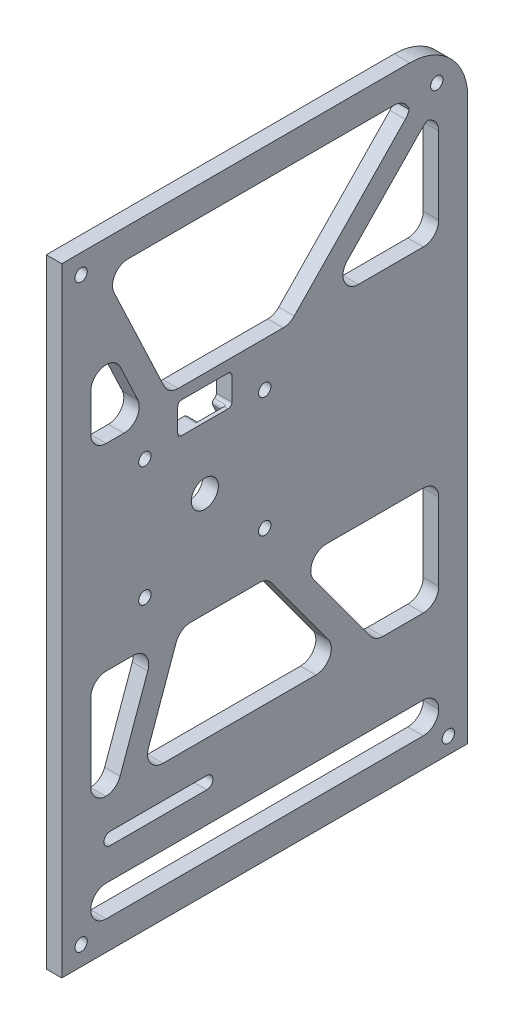
SolidWorks part; units mm, degrees
ref_plane "Front Plane" through (0, 0, 0) normal (0, 0, 1) x (1, 0, 0)
ref_plane "Top Plane" through (0, 0, 0) normal (0, 1, 0) x (1, 0, 0)
ref_plane "Right Plane" through (0, 0, 0) normal (1, 0, 0) x (0, 0, -1)
sketch "Sketch2" plane through (0, 0, 0) normal (1, 0, 0) x (0, 0, -1)
  line L1 (0, 0) -> (105, 0)
  line L2 (0, 0) -> (0, 160)
  line L3 (0, 160) -> (90, 160)
  line L4 (105, 0) -> (105, 145)
  line L5 (10.8174, 152.5) -> (90, 152.5)
  line L8 (90, 145) -> (105, 160) construction
  line L9 (90, 145) -> (105, 145) construction
  line L11 (7.5, 152.5) -> (90, 152.5) construction
  line L12 (7.5, 7.5) -> (7.5, 152.5) construction
  line L13 (7.5, 7.5) -> (97.5, 7.5) construction
  line L14 (97.5, 7.5) -> (97.5, 145) construction
  line L17 (12.5, 25) -> (37.5, 25) construction
  line L22 (12.5, 26.6) -> (37.5, 26.6)
  line L23 (12.5, 23.4) -> (37.5, 23.4)
  line L24 (7.5, 35) -> (7.5, 63)
  line L25 (97.5, 35) -> (97.5, 63)
  line L35 (37, 121.859) -> (37, 90) construction
  line L36 (37, 90) -> (7.5, 152.5) construction
  line L44 (44, 106) -> (30, 106)
  line L49 (44, 106) -> (44, 114)
  line L50 (44, 114) -> (30, 114)
  line L51 (30, 106) -> (30, 114)
  line L52 (44, 106) -> (30, 114) construction
  line L53 (44, 114) -> (30, 106) construction
  line L62 (58.9543, 117) -> (27.5734, 117)
  line L97 (37, 90) -> (7.5, 7.5) construction
  line L98 (24.1594, 63) -> (14.1473, 35)
  line L99 (7.5, 145.4716) -> (7.5, 114)
  line L100 (97, 152) -> (37, 90) construction
  line L102 (90, 152.5) -> (90, 149.0806)
  line L103 (90, 160) -> (105, 160) construction
  line L104 (105, 160) -> (105, 145) construction
  line L106 (97.5, 145) -> (97.5, 117)
  line L107 (94.4006, 145) -> (67.3038, 117)
  line L108 (94.4006, 145) -> (97.5, 145)
  line L109 (90, 149.0806) -> (58.9543, 117)
  line L110 (67.3038, 117) -> (97.5, 117)
  line L115 (97.5, 7.5) -> (7.5, 7.5)
  line L118 (97.5, 35) -> (81.0535, 35)
  line L119 (97.5, 63) -> (60.5202, 63)
  line L120 (30.5315, 63) -> (20.5194, 35)
  line L121 (24.1594, 63) -> (7.5, 63)
  line L122 (37, 90) -> (97.5, 7.5) construction
  line L123 (22.3546, 114) -> (7.5, 114)
  line L124 (53.0798, 63) -> (73.6131, 35)
  line L125 (34.1752, 91.0101) -> (4.6752, 8.5101) construction
  line L126 (27.5734, 117) -> (10.8174, 152.5)
  line L127 (22.3546, 114) -> (7.5, 145.4716)
  line L128 (53.0798, 63) -> (30.5315, 63)
  line L129 (39.8248, 88.9899) -> (10.3248, 6.4899) construction
  line L130 (14.1473, 35) -> (7.5, 35)
  line L133 (7.5, 15.5) -> (97.5, 15.5)
  line L134 (60.5202, 63) -> (81.0535, 35)
  line L135 (34.5808, 88.2259) -> (95.0808, 5.7259) construction
  line L136 (73.6131, 35) -> (20.5194, 35)
  line L140 (7.5, 15.5) -> (7.5, 7.5)
  line L141 (97.5, 15.5) -> (97.5, 7.5)
  arc A0 (90, 160) -> (105, 145) centre (90, 145) cw
  circle A11 centre (97, 152) radius 1.6
  arc A16 (12.5, 26.6) -> (12.5, 23.4) centre (12.5, 25) ccw
  arc A17 (37.5, 23.4) -> (37.5, 26.6) centre (37.5, 25) ccw
  circle A19 centre (52.5, 105.5) radius 1.6
  circle A22 centre (37, 90) radius 3.5
  circle A24 centre (52.5, 74.5) radius 1.6
  circle A25 centre (21.5, 74.5) radius 1.6
  circle A26 centre (21.5, 105.5) radius 1.6
  arc A28 (90, 152.5) -> (97.5, 145) centre (90, 145) cw construction
  circle A29 centre (5, 5) radius 1.6
  circle A30 centre (100, 4.1732) radius 1.6
  circle A31 centre (5, 155) radius 1.6
  point P27 (95.2179, 153.7533)
  point P28 (34.2179, 91.7533)
  point P34 (25, 25)
  point P43 (98.7821, 150.2467)
  point P47 (37.7821, 88.2467)
  point P52 (37, 110)
  point P53 (46.5, 99)
  point P58 (46.5, 115)
  point P59 (25.5, 115)
  point P60 (25.5, 99)
  point P66 (37.9972, 91.5038)
  point P67 (37, 90)
  point P75 (38.2565, 91.0762)
  point P76 (7.2565, 156.0762)
  point P77 (33.7435, 88.9238)
  point P78 (2.7435, 153.9238)
  point P85 (101.9972, 6.5038)
  dimension "D1" = 15
  dimension "D6" = 3.2
  dimension "D7" = 5
  dimension "D8" = 8
  dimension "D9" = 5
  dimension "D10" = 4.1732
  dimension "D11" = 8
  dimension "D12" = 7.5
  dimension "D13" = 6
  dimension "D14" = 3.2
  dimension "D15" = 25
  dimension "D19" = 5
  dimension "D20" = 37
  dimension "D21" = 3.2
  dimension "D22" = 70
  dimension "D23" = 15.5
  dimension "D34" = 7
  dimension "D36" = 7.5
  dimension "D2" = 160
  dimension "D3" = 105
  dimension "D5" = 45
  dimension "D16" = 7.5
  dimension "D17" = 10
  dimension "D18" = 25
  dimension "D24" = 15.5
  dimension "D25" = 20
  dimension "D26" = 3
  dimension "D27" = 3
  dimension "D28" = 4
  dimension "D29" = 31
  dimension "D31" = 8
  dimension "D30" = 14
  dimension "D33" = 31
  dimension "D35" = 3
  dimension "D32" = 3
  dimension "D37" = 27
  dimension "D38" = 7.5
  dimension "D39" = 7.5
  dimension "D40" = 5
  dimension "D41" = 5
  dimension "D42" = 5
  dimension "D43" = 7.5
  dimension "D46" = 3
  dimension "D48" = 3
  dimension "D49" = 12.5
  dimension "D4" = 7.5
  dimension "D44" = 3
  dimension "D45" = 3
  dimension "D47" = 3
extrude "Boss-Extrude1" add sketch "Sketch2" along normal blind 4
chamfer "Chamfer1" distance 1.5 angle 45 8 edges at (0, 105.5, -54.1) (0, 155, -6.6) (0, 152, -98.6) (0, 74.5, -54.1) (0, 74.5, -23.1) (0, 105.5, -23.1) (0, 4.1732, -101.6) (0, 5, -6.6)
fillet "Fillet2" radius 1 4 edges at (2, 114, -44) (2, 106, -44) (2, 106, -30) (2, 114, -30)
fillet "Fillet3" radius 4 28 edges at (2, 152.5, -90) (2, 145, -97.5) (2, 117, -97.5) (2, 117, -67.3038) (2, 145, -94.4006) (2, 149.0806, -90) (2, 117, -27.5734) (2, 145.4716, -7.5) (2, 114, -7.5) (2, 114, -22.3546) (2, 63, -7.5) (2, 63, -24.1594) (2, 35, -14.1473) (2, 35, -7.5) (2, 35, -20.5194) (2, 35, -73.6131) (2, 35, -97.5) (2, 35, -81.0535) (2, 63, -97.5) (2, 63, -30.5315) (2, 63, -53.0798) (2, 63, -60.5202) (2, 117, -58.9543) (2, 152.5, -10.8174) (2, 7.5, -7.5) (2, 15.5, -7.5) (2, 7.5, -97.5) (2, 15.5, -97.5)
sketch "Sketch3" plane through (0, 0, 0) normal (-1, 0, 0) x (0, 0, 1)
  line L0 (-105, 95.5) -> (-52.5, 95.5) construction
  line L1 (-105, 0) -> (-105, 145) construction
  line L4 (-39.5, 106) -> (-38.9808, 107.9314) construction
  line L5 (-52.5, 95.5) -> (-42.3226, 95.5) construction
  line L6 (-37, 121.859) -> (-37, 90) construction
  line L7 (-44, 106) -> (-30, 106) construction
  line L8 (-105, 92.5) -> (-52.5, 92.5)
  line L9 (-36.6029, 105.2212) -> (-36.0837, 107.1526)
  line L10 (-105, 98.5) -> (-52.5, 98.5)
  line L11 (-42.3971, 106.7788) -> (-41.8779, 108.7102)
  line L12 (-52.5, 105.5) -> (-52.5, 74.5) construction
  line L13 (-105, 92.5) -> (-105, 98.5)
  line L14 (-36.0837, 107.1526) -> (-41.8779, 108.7102)
  line L17 (-42.3226, 95.5) -> (-39.5, 106) construction
  line L19 (-97, 152) -> (-37, 90) construction
  spline S0 degree 2 poles (-52.5, 95.5) (-42.3226, 95.5) (-39.5, 106) knots 0 0 0 1 1 1 construction
  spline S1 degree 1 poles (-52.5, 92.5) (-36.6029, 105.2212) knots 0 0 1 1 construction
  spline S2 degree 3 poles (-52.5, 92.5) (-52.0179, 92.5) (-51.0448, 92.5315) (-49.1758, 92.7252) (-46.9363, 93.2222) (-44.4522, 94.2535) (-42.2241, 95.7235) (-40.3092, 97.5997) (-38.7341, 99.8266) (-37.6975, 101.9403) (-37.0242, 103.7646) (-36.7331, 104.7367) (-36.6029, 105.2212) knots 0 0 0 0 0.0625 0.125 0.25 0.375 0.5 0.625 0.75 0.875 0.9375 1 1 1 1
  spline S3 degree 1 poles (-52.5, 98.5) (-42.3971, 106.7788) knots 0 0 1 1 construction
  spline S4 degree 3 poles (-52.5, 98.5) (-52.1527, 98.5) (-51.4407, 98.5232) (-50.1604, 98.6576) (-48.7274, 98.9809) (-47.274, 99.5903) (-46.0218, 100.417) (-44.9165, 101.4946) (-43.9317, 102.8748) (-43.2157, 104.3229) (-42.7222, 105.6559) (-42.4966, 106.4087) (-42.3971, 106.7788) knots 0 0 0 0 0.0625 0.125 0.25 0.375 0.5 0.625 0.75 0.875 0.9375 1 1 1 1
  dimension "D4" = 2
  dimension "D1" = 3
  dimension "D3" = 10
  dimension "D6" = 2.5
  dimension "D2" = 3
extrude "Cut-Extrude1" cut sketch "Sketch3" against normal blind 3
sketch "Sketch4" plane through (0, 0, 0) normal (-1, 0, 0) x (0, 0, 1)
  line L1 (-82.5, 98.5) -> (-77.5, 98.5)
  line L2 (-82.5, 98.5) -> (-82.5, 95.5)
  line L3 (-82.5, 95.5) -> (-77.5, 95.5)
  line L4 (-77.5, 98.5) -> (-77.5, 95.5)
  line L6 (-105, 92.5) -> (-100, 92.5)
  line L7 (-105, 92.5) -> (-105, 95.5)
  line L8 (-105, 95.5) -> (-100, 95.5)
  line L9 (-100, 92.5) -> (-100, 95.5)
  line L10 (-55, 92.5) -> (-60, 92.5)
  line L11 (-55, 92.5) -> (-55, 95.5)
  line L12 (-55, 95.5) -> (-60, 95.5)
  line L13 (-60, 92.5) -> (-60, 95.5)
  line L14 (-52.5, 98.5) -> (-105, 98.5) construction
  line L17 (-105, 92.5) -> (-52.5, 92.5) construction
  dimension "D1" = 5
  dimension "D2" = 5
  dimension "D3" = 5
  dimension "D4" = 3
  dimension "D5" = 3
  dimension "D6" = 3
  dimension "D7" = 17.5
  dimension "D8" = 17.5
extrude "Boss-Extrude2" add sketch "Sketch4" against normal blind 1
chamfer "Chamfer2" distance 1 angle 45 3 edges at (1, 92.5, -57.5) (1, 98.5, -80) (1, 92.5, -102.5)
fillet "Fillet4" radius 1 8 edges at (0.5, 95.5, -55) (0.5, 95.5, -100) (0.5, 95.5, -60) (0.5, 95.5, -77.5) (0.5, 95.5, -82.5) (0.5, 95.5, -105) (1.5, 106, -36.3935) (1.5, 106, -42.6235)
